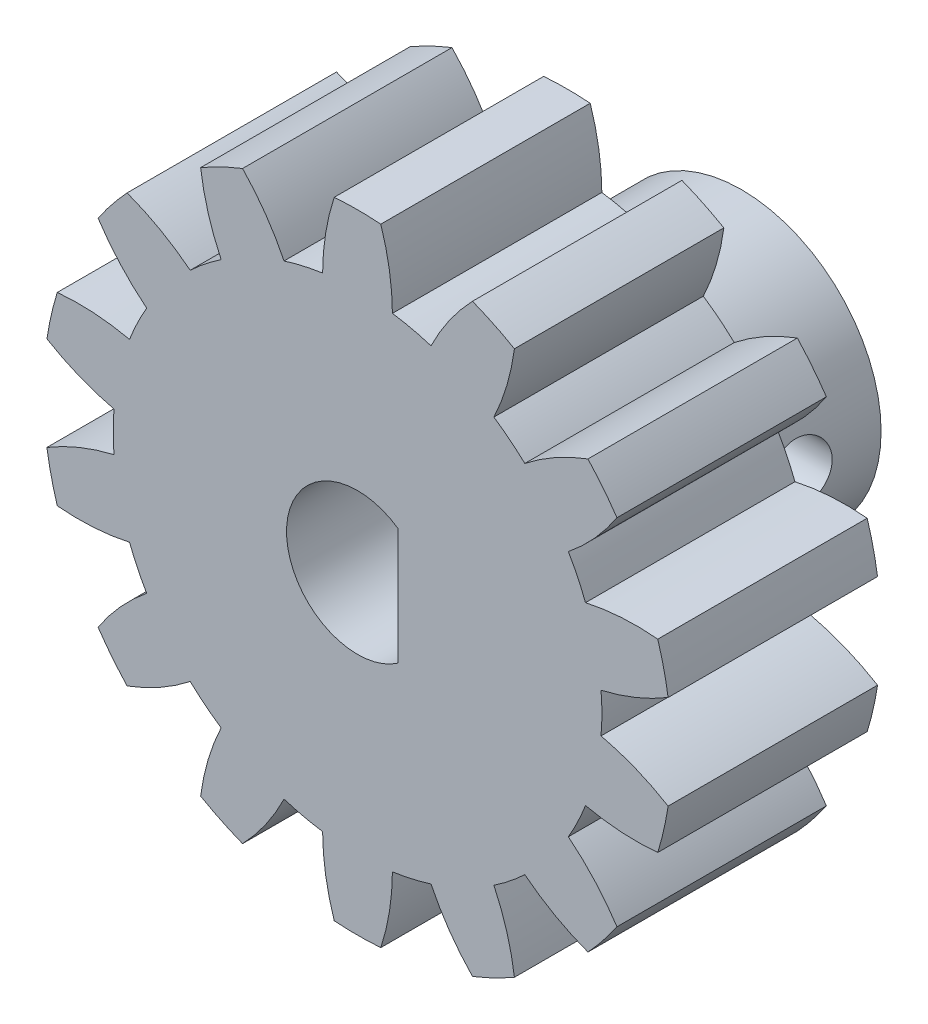
SolidWorks part; units mm, degrees
note: The reader was unsure of these and kept them because the rebuilt part matched: shared geometry of "Sketch2<4>".
ref_plane "Front Plane" through (0, 0, 0) normal (0, 0, 1) x (1, 0, 0)
ref_plane "Top Plane" through (0, 0, 0) normal (0, 1, 0) x (1, 0, 0)
ref_plane "Right Plane" through (0, 0, 0) normal (1, 0, 0) x (0, 0, -1)
sketch "Sketch1" plane through (0, 0, 0) normal (0, 0, 1) x (1, 0, 0)
  circle A12 centre (-24.1927, -27.8293) radius 6
  circle A15 centre (-24.1927, -27.8293) radius 3.05
  dimension "D3" = 12
  dimension "D1" = 6.1
extrude "Boss-Extrude1" add sketch "Sketch1" along normal up to vertex (7.5 mm away)
sketch "Sketch2" plane through (0, 0, 7.5) normal (0, 0, 1) x (1, 0, 0)
  line L0 (-24.1927, -14.3293) -> (-24.1927, -41.3293) construction
  circle A33 centre (-24.1927, -27.8293) radius 13.5
  circle A48 centre (-24.1927, -27.8293) radius 10.5
  circle A62 centre (-24.1927, -27.8293) radius 6 construction
  arc A63 (-25.1927, -14.3664) -> (-25.6927, -17.437) centre (-15.6928, -17.4893) ccw
  arc A64 (-23.1927, -14.3664) -> (-22.6927, -17.437) centre (-32.6925, -17.4893) cw
  point P1 (-18.1927, -27.8293)
  point P3 (-24.1927, -27.8293)
  point P13 (-16.5422, -25.4903)
  dimension "D1" = 27
  dimension "D3" = 2
  dimension "D4" = 10
  dimension "D5" = 3
  dimension "D2" = 3
extrude "Boss-Extrude3" add sketch "Sketch2" along normal blind 9
extrude "Boss-Extrude4" add sketch "Sketch2<4>" along normal up to surface (9 mm away) contours A33 L0 A48 A64 | L0 A33 A63 A48
sketch "Sketch2<4>" plane through (0, 0, 7.5) normal (0, 0, 1) x (1, 0, 0) same geometry as "Sketch2"
pattern_circular "CirPattern1" count 14 over 360 about axis through (-24.1927, -27.8293, 0) along (0, 0, 1) of "Boss-Extrude4"
sketch "Sketch3" plane through (0, 0, 7.5) normal (0, 0, -1) x (-1, 0, 0)
  circle A0 centre (24.1927, -27.8293) radius 3.05 construction
  circle A1 centre (24.1927, -27.8293) radius 3.05
extrude "Cut-Extrude1" cut sketch "Sketch3" against normal through all
sketch "Sketch5" plane through (0, 0, 0) normal (0, 0, -1) x (-1, 0, 0)
  line L1 (21.1427, -22.6623) -> (22.4427, -22.6623)
  line L2 (21.1427, -22.6623) -> (21.1427, -31.6503)
  line L3 (21.1427, -31.6503) -> (22.4427, -31.6503)
  line L4 (22.4427, -22.6623) -> (22.4427, -31.6503)
  circle A0 centre (24.1927, -27.8293) radius 6 construction
  circle A1 centre (24.1927, -27.8293) radius 3.05 construction
  dimension "D1" = 1.3
extrude "Boss-Extrude5" add sketch "Sketch5" against normal through all
sketch "Sketch4" plane through (0, 0, 0) normal (1, 0, 0) x (0, 0, -1)
  circle A1 centre (-3.5, -27.8293) radius 1.4
  circle A2 centre (-3.5, -27.8293) radius 1.4
  dimension "D1" = 0
extrude "Cut-Extrude2" cut sketch "Sketch4" against normal through all both and the other way through all
